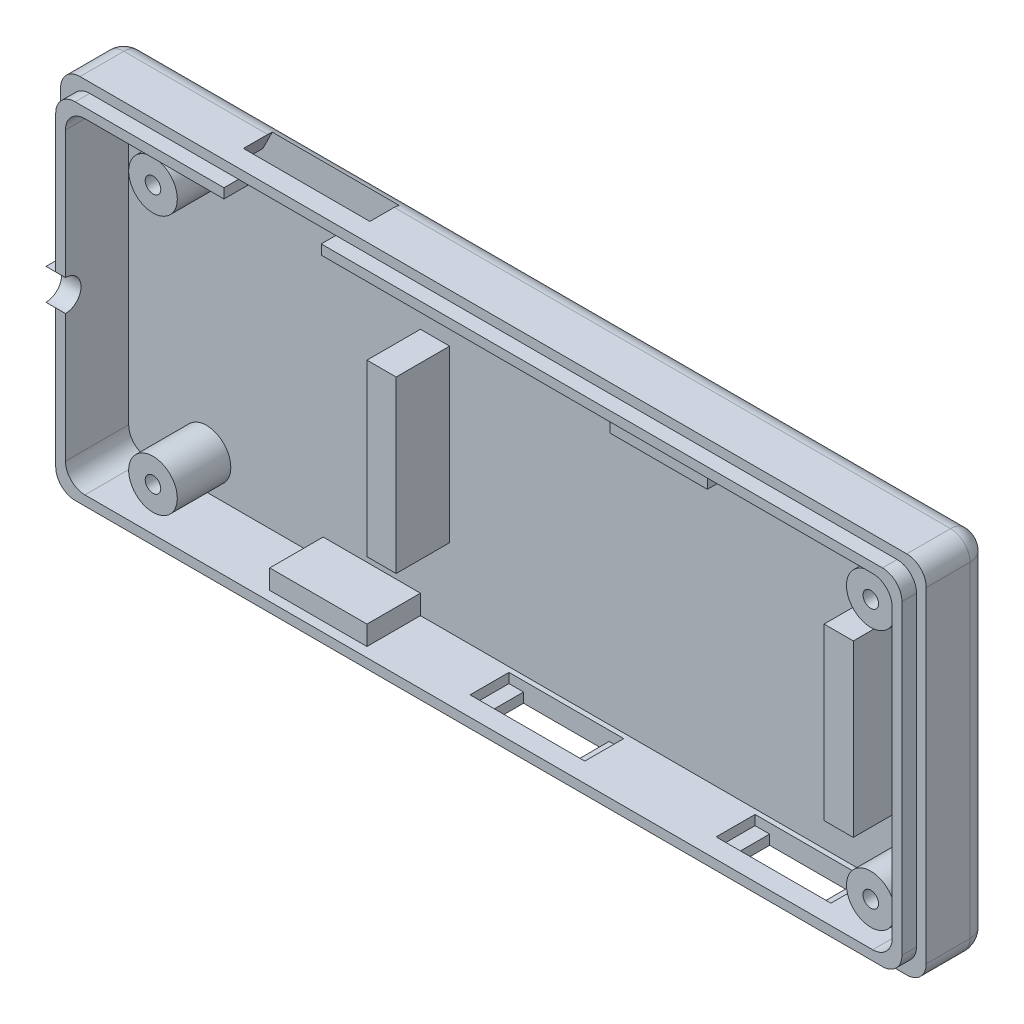
SolidWorks part; units mm, degrees
ref_plane "前视基准面" through (0, 0, 0) normal (0, 0, 1) x (1, 0, 0)
ref_plane "上视基准面" through (0, 0, 0) normal (0, 1, 0) x (1, 0, 0)
ref_plane "右视基准面" through (0, 0, 0) normal (1, 0, 0) x (0, 0, -1)
sketch "草图1" plane through (0, 0, 0) normal (0, 0, 1) x (1, 0, 0)
  line L1 (0, 0) -> (89, 0)
  line L2 (0, 0) -> (0, -37.5)
  line L3 (0, -37.5) -> (89, -37.5)
  line L4 (89, 0) -> (89, -37.5)
  dimension "D1" = 89
  dimension "D2" = 37.5
extrude "凸台-拉伸1" add sketch "草图1" along normal blind 8
sketch "草图2" plane through (0, 0, 8) normal (0, 0, 1) x (1, 0, 0)
  line L0 (0, 0) -> (0, -37.5) construction
  line L1 (2, -2) -> (87, -2)
  line L2 (2, -2) -> (2, -35.5)
  line L3 (2, -35.5) -> (87, -35.5)
  line L4 (87, -2) -> (87, -35.5)
  line L5 (89, 0) -> (0, 0) construction
  line L6 (89, -37.5) -> (89, 0) construction
  line L7 (0, -37.5) -> (89, -37.5) construction
  dimension "D1" = 2
  dimension "D2" = 2
  dimension "D3" = 2
  dimension "D4" = 2
extrude "切除-拉伸1" cut sketch "草图2" against normal blind 6.5
fillet "圆角2" radius 2 4 edges at (44.5, -37.5, 0) (89, -18.75, 0) (44.5, 0, 0) (0, -18.75, 0)
fillet "圆角3" radius 2 1 edges at (87, -35.5, 4.75)
fillet "圆角4" radius 2 1 edges at (87, -2, 4.75)
fillet "圆角5" radius 2 1 edges at (2, -35.5, 4.75)
fillet "圆角6" radius 2 1 edges at (2, -2, 4.75)
fillet "圆角7" radius 2 8 edges at (0.5858, -36.9142, 0.5858) (0.5858, -0.5858, 0.5858) (88.4142, -0.5858, 0.5858) (88.4142, -36.9142, 0.5858) (0, -37.5, 5) (0, 0, 5) (89, 0, 5) (89, -37.5, 5)
sketch "草图3" plane through (0, 0, 1.5) normal (0, 0, 1) x (1, 0, 0)
  line L0 (4, -35.5) -> (85, -35.5) construction
  line L1 (87, -33.5) -> (87, -4) construction
  line L2 (85, -2) -> (4, -2) construction
  line L3 (85, -2) -> (4, -2) construction
  line L4 (2, -4) -> (2, -33.5) construction
  line L5 (4, -35.5) -> (85, -35.5) construction
  line L6 (57, -2) -> (67, -2)
  line L7 (57, -2) -> (57, -4)
  line L8 (57, -4) -> (67, -4)
  line L9 (67, -2) -> (67, -4)
  line L10 (22, -35.5) -> (32, -35.5)
  line L11 (22, -35.5) -> (22, -33.5)
  line L12 (22, -33.5) -> (32, -33.5)
  line L13 (32, -35.5) -> (32, -33.5)
  line L14 (87, -33.5) -> (87, -4) construction
  line L15 (79, -10) -> (82, -10)
  line L16 (79, -10) -> (79, -27.5)
  line L17 (79, -27.5) -> (82, -27.5)
  line L18 (82, -10) -> (82, -27.5)
  line L20 (32, -10) -> (35, -10)
  line L21 (32, -10) -> (32, -27.5)
  line L22 (32, -27.5) -> (35, -27.5)
  line L23 (35, -10) -> (35, -27.5)
  circle A0 centre (83.8, -5.4) radius 2.5
  circle A1 centre (83.8, -32.1) radius 2.5
  circle A2 centre (10, -5.4) radius 2.5
  circle A3 centre (10, -32.0536) radius 2.5
  point P34 (87, -18.75)
  dimension "D1" = 5
  dimension "D2" = 5
  dimension "D3" = 5
  dimension "D4" = 5
  dimension "D7" = 3.2
  dimension "D12" = 20
  dimension "D5" = 3.4
  dimension "D6" = 3.2
  dimension "D8" = 3.4
  dimension "D9" = 3.4
  dimension "D10" = 8
  dimension "D11" = 8
  dimension "D13" = 10
  dimension "D14" = 2
  dimension "D15" = 20
  dimension "D16" = 10
  dimension "D17" = 2
  dimension "D18" = 3
  dimension "D19" = 8
  dimension "D20" = 8
  dimension "D21" = 5
  dimension "D22" = 3
  dimension "D23" = 17.5
  dimension "D24" = 8
  dimension "D25" = 44
extrude "凸台-拉伸2" add sketch "草图3" along normal blind 5.5
sketch "草图4" plane through (0, 0, 7) normal (0, 0, 1) x (1, 0, 0)
  circle A0 centre (10, -5.4) radius 0.8
  dimension "D1" = 1.6
extrude "切除-拉伸2" cut sketch "草图4" against normal through all
sketch "草图5" plane through (0, 0, 7) normal (0, 0, 1) x (1, 0, 0)
  circle A0 centre (83.8, -5.4) radius 0.8
  dimension "D1" = 1.6
extrude "切除-拉伸3" cut sketch "草图5" against normal through all
sketch "草图6" plane through (0, 0, 7) normal (0, 0, 1) x (1, 0, 0)
  circle A0 centre (10, -32.0536) radius 0.8
  dimension "D1" = 1.6
extrude "切除-拉伸4" cut sketch "草图6" against normal through all
sketch "草图8" plane through (0, 0, 7) normal (0, 0, 1) x (1, 0, 0)
  circle A0 centre (83.8, -32.1) radius 0.8
  dimension "D1" = 1.6
extrude "切除-拉伸5" cut sketch "草图8" against normal through all
sketch "草图9" plane through (0, 0, 0) normal (0, 0, -1) x (-1, 0, 0)
  circle A0 centre (-83.8, -5.4) radius 2
  circle A1 centre (-10, -5.4) radius 2
  circle A2 centre (-10, -32.0536) radius 2
  circle A3 centre (-83.8, -32.1) radius 2
  dimension "D1" = 4
  dimension "D2" = 4
  dimension "D3" = 4
  dimension "D4" = 4
extrude "切除-拉伸6" cut sketch "草图9" against normal blind 1
sketch "草图10" plane through (0, 0, 0) normal (-1, 0, 0) x (0, 0, 1)
  line L0 (8, -2) -> (8, -35.5) construction
  line L1 (8, -17.15) -> (8, -20.35)
  arc A0 (8, -17.15) -> (8, -20.35) centre (8, -18.75) ccw
  dimension "D1" = 1.6
extrude "切除-拉伸7" cut sketch "草图10" against normal blind 2
sketch "草图11" plane through (0, -37.5, 0) normal (0, -1, 0) x (1, 0, 0)
  line L0 (2, 2) -> (87, 2) construction
  line L1 (77.2, 2) -> (68.4, 2)
  line L2 (77.2, 2) -> (77.2, 6)
  line L3 (77.2, 6) -> (68.4, 6)
  line L4 (68.4, 2) -> (68.4, 6)
  line L5 (87, 2) -> (87, 8) construction
  line L6 (51.9, 2) -> (43.1, 2)
  line L7 (51.9, 2) -> (51.9, 6)
  line L8 (51.9, 6) -> (43.1, 6)
  line L9 (43.1, 2) -> (43.1, 6)
  dimension "D1" = 9.8
  dimension "D2" = 8.8
  dimension "D3" = 16.5
  dimension "D4" = 8.8
  dimension "D5" = 4
  dimension "D6" = 4
extrude "切除-拉伸8" cut sketch "草图11" against normal blind 2
sketch "草图12" plane through (0, -35.5, 0) normal (0, 1, 0) x (1, 0, 0)
  line L0 (51.9, -2) -> (68.4, -2) construction
  line L1 (66.9, -2) -> (78.7, -2)
  line L2 (66.9, -2) -> (66.9, -6)
  line L3 (66.9, -6) -> (78.7, -6)
  line L4 (78.7, -2) -> (78.7, -6)
  line L5 (2, -2) -> (43.1, -2) construction
  line L6 (41.6, -2) -> (53.4, -2)
  line L7 (41.6, -2) -> (41.6, -6)
  line L8 (41.6, -6) -> (53.4, -6)
  line L9 (53.4, -2) -> (53.4, -6)
  line L10 (77.2, -2) -> (77.2, -6) construction
  line L11 (68.4, -6) -> (68.4, -2) construction
  line L12 (51.9, -2) -> (51.9, -6) construction
  line L13 (43.1, -6) -> (43.1, -2) construction
  dimension "D1" = 1.5
  dimension "D2" = 1.5
  dimension "D3" = 4
  dimension "D4" = 1.5
  dimension "D5" = 1.5
  dimension "D6" = 4
extrude "切除-拉伸9" cut sketch "草图12" against normal blind 1
sketch "草图13" plane through (0, 0, 8) normal (0, 0, 1) x (1, 0, 0)
  line L0 (29.8, 0) -> (30.8, -2)
  line L1 (87, 0) -> (2, 0) construction
  line L2 (85, -2) -> (4, -2) construction
  line L3 (30.8, -2) -> (15.8, -2)
  line L4 (15.8, -2) -> (16.8, 0)
  line L5 (16.8, 0) -> (29.8, 0)
  line L6 (89, -35.5) -> (89, -2) construction
  dimension "D1" = 59.2
  dimension "D2" = 13
  dimension "D3" = 15
  dimension "D4" = 1
extrude "切除-拉伸10" cut sketch "草图13" against normal blind 6.5
sketch "草图14" plane through (0, 0, 8) normal (0, 0, 1) x (1, 0, 0)
  line L5 (15.8, -2) -> (16.8, 0)
  line L6 (16.8, 0) -> (29.8, 0)
  line L7 (15.8, -2) -> (30.8, -2)
  line L8 (30.8, -2) -> (29.8, 0)
extrude "凸台-拉伸3" add sketch "草图14" against normal blind 3.5
sketch "草图15" plane through (0, 0, 8) normal (0, 0, 1) x (1, 0, 0)
  line L0 (2, 0) -> (87, 0)
  line L5 (89, -2) -> (89, -35.5)
  line L6 (87, -37.5) -> (2, -37.5)
  line L7 (0, -35.5) -> (0, -20.35)
  line L8 (0, -20.35) -> (1, -20.35)
  line L9 (2, -20.35) -> (0, -20.35) construction
  line L10 (1, -20.35) -> (1, -34.5)
  line L11 (3, -36.5) -> (86, -36.5)
  line L12 (88, -34.5) -> (88, -3)
  line L13 (86, -1) -> (3, -1)
  line L14 (1, -3) -> (1, -17.15)
  line L15 (2, -17.15) -> (0, -17.15) construction
  line L16 (1, -17.15) -> (0, -17.15)
  line L17 (0, -17.15) -> (0, -2)
  arc A0 (87, 0) -> (89, -2) centre (87, -2) cw
  arc A1 (89, -35.5) -> (87, -37.5) centre (87, -35.5) cw
  arc A2 (2, -37.5) -> (0, -35.5) centre (2, -35.5) cw
  arc A3 (0, -2) -> (2, 0) centre (2, -2) cw
  arc A4 (3, -1) -> (1, -3) centre (3, -3) ccw
  arc A5 (88, -3) -> (86, -1) centre (86, -3) ccw
  arc A6 (86, -36.5) -> (88, -34.5) centre (86, -34.5) ccw
  arc A7 (1, -34.5) -> (3, -36.5) centre (3, -34.5) ccw
  dimension "D4" = 2
  dimension "D5" = 2
  dimension "D6" = 2
  dimension "D7" = 2
  dimension "D1" = 1
  dimension "D2" = 1
  dimension "D3" = 1
extrude "切除-拉伸12" cut sketch "草图15" against normal blind 1.5
sketch "草图18" plane through (0, -2, 0) normal (0, -1, 0) x (-1, 0, 0)
  line L3 (-18.3, -8) -> (-28.3, -8)
  line L4 (-28.3, -4.5) -> (-28.3, -8)
  line L5 (-30.8, -1.5) -> (-30.8, -4.5) construction
  line L6 (-28.3, -4.5) -> (-18.3, -4.5)
  line L7 (-15.8, -4.5) -> (-30.8, -4.5) construction
  line L8 (-18.3, -4.5) -> (-18.3, -8)
  dimension "D1" = 10
  dimension "D2" = 2.5
  dimension "D3" = 3.5
extrude "切除-拉伸15" cut sketch "草图18" against normal blind 1
